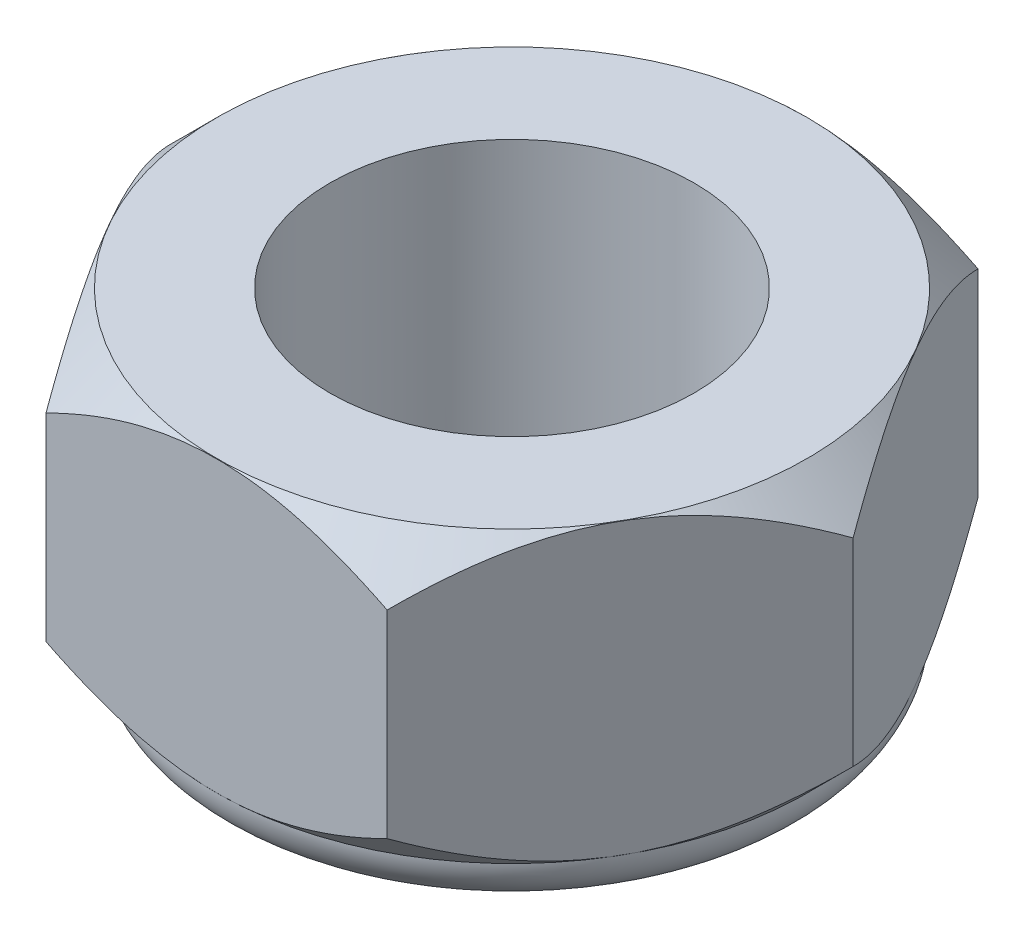
SolidWorks part; units mm, degrees
material "1023 Carbon Steel Sheet (SS)"
ref_plane "Front" through (0, 0, 0) normal (0, 0, 1) x (1, 0, 0)
ref_plane "Top" through (0, 0, 0) normal (0, 1, 0) x (1, 0, 0)
ref_plane "Right" through (0, 0, 0) normal (1, 0, 0) x (0, 0, -1)
sketch "Sketch1" plane through (0, 0, 0) normal (0, 1, 0) x (1, 0, 0)
  line L0 (0, 0) -> (0, -50000) construction
  line L1 (3.7095, -6.425) -> (7.419, 0)
  line L2 (7.419, 0) -> (3.7095, 6.425)
  line L3 (3.7095, 6.425) -> (-3.7095, 6.425)
  line L4 (-3.7095, 6.425) -> (-7.419, 0)
  line L5 (-7.419, 0) -> (-3.7095, -6.425)
  line L6 (-3.7095, -6.425) -> (3.7095, -6.425)
  circle A0 centre (0, 0) radius 3.5
  circle A1 centre (0, 0) radius 6.425 construction
  dimension "D1" = 7
  dimension "D2" = 12.85
  dimension "D3" = 3.7095
extrude "Boss-Extrude1" add sketch "Sketch1" along normal blind 6.3
sketch "Sketch3" plane through (0, 0, 0) normal (0, 0, 1) x (1, 0, 0)
  line L0 (7.419, 3.15) -> (-7.422, 3.15) construction
  line L1 (7.419, 6.3) -> (7.419, 0) construction
  line L2 (-10.2312, 6.3) -> (-1.4791, 6.3) construction
  line L3 (3.5, 6.3) -> (-3.5, 6.3) construction
  line L4 (-9.6048, 0) -> (49990.3952, 0) construction
  line L5 (-3.5, 0) -> (3.5, 0) construction
  line L6 (-7.422, 7.9138) -> (-7.422, 7.5238) construction
  line L7 (-6.422, 6.8) -> (-6.422, 6.3)
  line L8 (-7.922, 6.8) -> (-6.422, 6.8)
  line L9 (-7.922, 5.3) -> (-7.922, 6.8)
  line L10 (-7.422, 5.3) -> (-7.922, 5.3)
  line L11 (-7.422, 1) -> (-6.422, 0)
  line L12 (-7.422, 1) -> (-7.922, 1)
  line L13 (-7.922, 1) -> (-7.922, -0.5)
  line L14 (-7.922, -0.5) -> (-6.422, -0.5)
  line L15 (-6.422, -0.5) -> (-6.422, 0)
  line L16 (-7.422, 5.3) -> (-6.422, 6.3)
  line L17 (0, 0) -> (0, 50000) construction
  dimension "D1" = 1.5
  dimension "D2" = 1.5
revolve "Cut-Revolve4" cut sketch "Sketch3" angle 360 about L17
hole_wizard "5/16-24 Tapped Hole4" positions "Sketch24" profile "Sketch23" tap size "5/16-24" standard "ANSI Inch"
sketch "Sketch24" plane through (0, 0, 0) normal (0, -1, 0) x (1, 0, 0)
  point P0 (0, 0)
sketch "Sketch23" plane through (0, 0, 0) normal (1, 0, 0) x (0, 0, -1)
  line L0 (0, 0) -> (0, 14.3794)
  line L1 (0, 14.3794) -> (3.96, 12)
  line L2 (3.96, 12) -> (3.96, 0)
  line L5 (3.96, 0) -> (0, 0)
  line L10 (0, 14.3794) -> (-3.96, 12) construction
  line L11 (0, -6.35) -> (0, 107.95) construction
  dimension "Tap Drill Dia." = 7.92
  dimension "Tap Drill Depth" = 12
  dimension "Drill Angle" = 118
cosmetic thread "Hole Thread2" parameters "D1"=8.3, "D2"=7.9375
sketch "Sketch27" plane through (0, 0, 0) normal (0, -1, 0) x (1, 0, 0)
  circle A0 centre (0, 0) radius 3.97
  circle A1 centre (0, 0) radius 6.422
  dimension "D1" = 7.94
  dimension "D2" = 12.8439
extrude "Boss-Extrude2" add sketch "Sketch27" along normal blind 1
fillet "Fillet2" radius 1 1 edges at (0, -1, -6.422)
fillet "Fillet3" radius 0.5 1 edges at (0, -1, -3.97)
